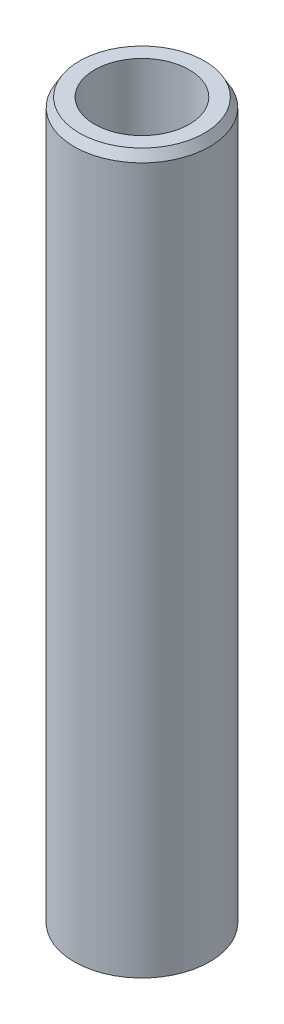
SolidWorks part; units mm, degrees
ref_plane "Front Plane" through (0, 0, 0) normal (0, 0, 1) x (1, 0, 0)
ref_plane "Top Plane" through (0, 0, 0) normal (0, 1, 0) x (1, 0, 0)
ref_plane "Right Plane" through (0, 0, 0) normal (1, 0, 0) x (0, 0, -1)
sketch "Sketch1" plane through (0, 0, 0) normal (0, 1, 0) x (1, 0, 0)
  circle A0 centre (0, 0) radius 37.5
  dimension "SHAFT_OD" = 75
extrude "Boss-Extrude1" add sketch "Sketch1" along normal blind 398.5163
sketch "Sketch2" plane through (0, 0, 0) normal (0, 1, 0) x (1, 0, 0)
  circle A0 centre (0, 0) radius 26.1693
  dimension "BORE_D" = 52.3386
extrude "Cut-Extrude1" cut sketch "Sketch2" along normal through all
chamfer "Chamfer1" distance 5.046 angle 30 2 edges at (0, 398.5163, 37.5) (0, 0, 37.5) first distance on face at (0, 398.5163, 37.5) first distance on face at (0, 0, 26.1693)
